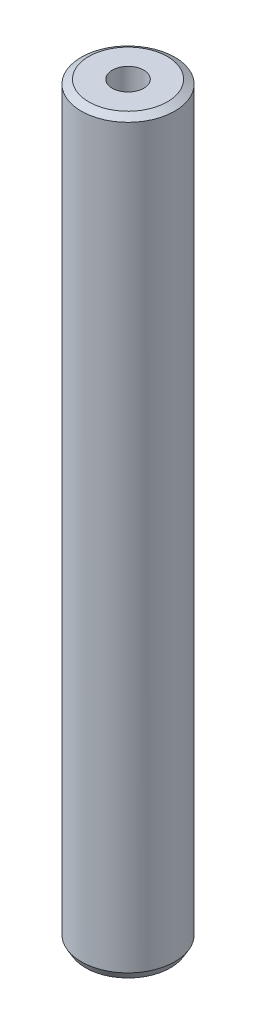
SolidWorks part; units mm, degrees
ref_plane "Front Plane" through (0, 0, 0) normal (0, 0, 1) x (1, 0, 0)
ref_plane "Top Plane" through (0, 0, 0) normal (0, 1, 0) x (1, 0, 0)
ref_plane "Right Plane" through (0, 0, 0) normal (1, 0, 0) x (0, 0, -1)
sketch "Sketch1" plane through (0, 0, 0) normal (0, 1, 0) x (1, 0, 0)
  circle A0 centre (0, 0) radius 37.5
  dimension "SHAFT_OD" = 75
extrude "Boss-Extrude1" add sketch "Sketch1" along normal blind 600
sketch "Sketch2" plane through (0, 0, 0) normal (0, 1, 0) x (1, 0, 0)
  circle A0 centre (0, 0) radius 12.6322
  dimension "BORE_D" = 25.2645
extrude "Cut-Extrude1" cut sketch "Sketch2" along normal through all
chamfer "Chamfer1" distance 3.4538 angle 60 2 edges at (0, 600, 37.5) (0, 0, 37.5) first distance on face at (0, 600, 37.5) first distance on face at (0, 0, 12.6322)
